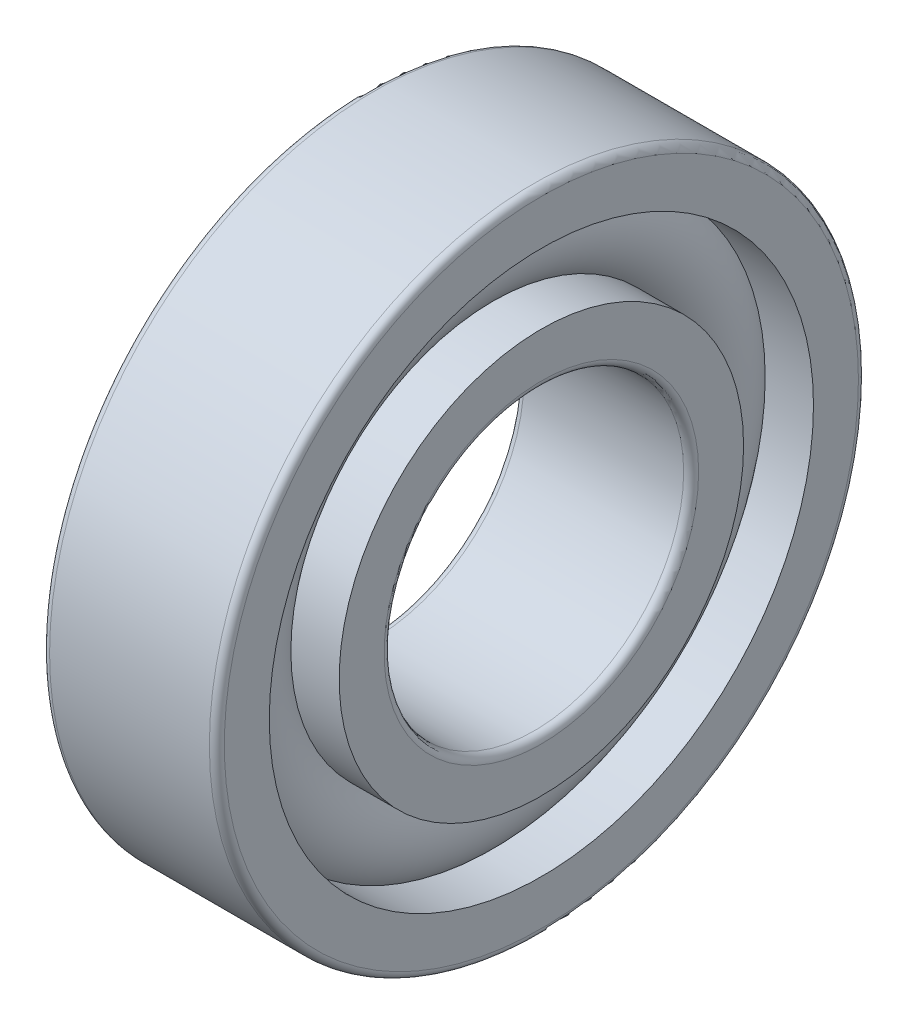
SolidWorks part; units mm, degrees
ref_plane "Plane1" through (0, 0, 0) normal (0, 0, 1) x (1, 0, 0)
ref_plane "Plane2" through (0, 0, 0) normal (0, 1, 0) x (1, 0, 0)
ref_plane "Plane3" through (0, 0, 0) normal (1, 0, 0) x (0, 0, -1)
other "Configuration Table"
sketch "Clipboard" plane through (0, 0, 0) normal (0, 0, 1) x (1, 0, 0)
  line L0 (-10, 0) -> (10, 0) construction
  line L1 (0, 0) -> (22.3471, -0.7804)
  line L2 (0, 0) -> (4.7471, 0.1658)
  line L3 (0, 0) -> (22.3471, -0.7804)
  line L4 (0, 0) -> (-22.3573, -0.3902)
  dimension "Count" = 2
sketch "CagSpiSke" plane through (0, 0, 0) normal (0, 0, 1) x (1, 0, 0)
  line L0 (0.105, 4.575) -> (0.105, 4.925)
  line L1 (0.105, 4.925) -> (-0.105, 4.925)
  line L2 (-0.105, 4.925) -> (-0.105, 4.575)
  line L3 (-0.105, 4.575) -> (0.105, 4.575)
  line L4 (-20.6375, 0) -> (20.6375, 0) construction
  line L5 (0, 0) -> (0, 23.7692) construction
revolve "CageSpine" add sketch "CagSpiSke" angle 0.001 about L4 reverse direction yes
ref_axis "Axis1" through (-50, 0, 0) along (1, 0, 0)
sketch "CagBalSke" plane through (0, 0, 0) normal (0, 0, 1) x (1, 0, 0)
  line L0 (-1.155, 4.75) -> (1.155, 4.75)
  line L1 (-1.905, 4.75) -> (1.905, 4.75) construction
  line L2 (-10, 0) -> (10, 0) construction
  line L3 (0, 0) -> (0, 24) construction
  arc A0 (1.155, 4.75) -> (-1.155, 4.75) centre (0, 4.75) cw
revolve "CageBall" [suppressed] add sketch "CagBalSke" angle 360 about L1 reverse direction yes
pattern_circular "CageBalls" [suppressed] count 2 every 180 about axis through (-50, 0, 0) along (1, 0, 0)
sketch "CagTrmODSke" plane through (0, 0, 0) normal (0, 0, 1) x (1, 0, 0)
  line L0 (1.156, 4.925) -> (1.156, 5.906)
  line L1 (1.156, 5.906) -> (-1.156, 5.906)
  line L2 (-1.156, 5.906) -> (-1.156, 4.925)
  line L3 (-1.156, 4.925) -> (1.156, 4.925)
  line L4 (-20.6375, 0) -> (20.6375, 0) construction
  line L5 (0, 0) -> (0, 25) construction
revolve "CageTrimOD" [suppressed] cut sketch "CagTrmODSke" angle 360 about L4 reverse direction yes
sketch "CagTrmIDSke" plane through (0, 0, 0) normal (0, 0, 1) x (1, 0, 0)
  line L0 (1.156, 3.596) -> (1.156, 4.575)
  line L1 (1.156, 4.575) -> (-1.156, 4.575)
  line L2 (-1.156, 4.575) -> (-1.156, 3.596)
  line L3 (-1.156, 3.596) -> (1.156, 3.596)
  line L4 (-20.6375, 0) -> (20.6375, 0) construction
  line L5 (0, 0) -> (0, 25) construction
revolve "CageTrimID" [suppressed] cut sketch "CagTrmIDSke" angle 360 about L4 reverse direction yes
sketch "BalSimSke" plane through (0, 0, 0) normal (0, 0, 1) x (1, 0, 0)
  line L0 (-10, 0) -> (10, 0) construction
  line L1 (-10, 4.75) -> (10, 4.75) construction
  line L2 (0, 0) -> (0, 23) construction
  circle A0 centre (0, 4.75) radius 1.05
revolve "BallsSimplified" add sketch "BalSimSke" angle 360 about L0
sketch "BalDetSke" plane through (0, 0, 0) normal (0, 0, 1) x (1, 0, 0)
  line L0 (-1.05, 4.75) -> (1.05, 4.75)
  line L1 (-1.905, 4.75) -> (1.905, 4.75) construction
  line L2 (0, 0) -> (0, 25) construction
  arc A0 (1.05, 4.75) -> (-1.05, 4.75) centre (0, 4.75) cw
revolve "BallDetailed" [suppressed] add sketch "BalDetSke" angle 360 about L1 reverse direction yes
sketch "InnRacSke" plane through (0, 0, 0) normal (0, 0, 1) x (1, 0, 0)
  line L0 (-0.7487, 4.05) -> (-1.75, 4.05)
  line L1 (-1.75, 4.05) -> (-1.75, 3.15)
  line L2 (-1.6, 3) -> (1.6, 3)
  line L3 (1.75, 3.15) -> (1.75, 4.05)
  line L4 (1.75, 4.05) -> (0.7487, 4.05)
  line L5 (-20.6375, 0) -> (20.6375, 0) construction
  line L6 (0, 0) -> (0, 30) construction
  arc A0 (-1.75, 3.15) -> (-1.6, 3) centre (-1.6, 3.15) ccw
  arc A1 (1.6, 3) -> (1.75, 3.15) centre (1.6, 3.15) ccw
  arc A2 (0.7487, 4.05) -> (-0.7487, 4.05) centre (0, 4.75) cw
revolve "InnerRace" add sketch "InnRacSke" angle 360 about L5 reverse direction yes
sketch "OutRacSke" plane through (0, 0, 0) normal (0, 0, 1) x (1, 0, 0)
  line L0 (-0.7487, 5.45) -> (-1.75, 5.45)
  line L1 (-1.75, 5.45) -> (-1.75, 6.35)
  line L2 (-1.6, 6.5) -> (1.6, 6.5)
  line L3 (1.75, 6.35) -> (1.75, 5.45)
  line L4 (1.75, 5.45) -> (0.7487, 5.45)
  line L5 (-20.6375, 0) -> (20.6375, 0) construction
  line L6 (0, 0) -> (0, 30) construction
  arc A0 (-1.75, 6.35) -> (-1.6, 6.5) centre (-1.6, 6.35) cw
  arc A1 (1.6, 6.5) -> (1.75, 6.35) centre (1.6, 6.35) cw
  arc A2 (0.7487, 5.45) -> (-0.7487, 5.45) centre (0, 4.75) ccw
revolve "OuterRace" add sketch "OutRacSke" angle 360 about L5 reverse direction yes
pattern_circular "BallsDetailed" [suppressed] count 2 every 180 about axis through (-50, 0, 0) along (1, 0, 0)
equation "\"BallCLRad@Clipboard\" = ( \"OD@OutRacSke\" + \"ID@InnRacSke\" ) / 4"
equation "\"BallCLRad@BalSimSke\" = \"BallCLRad@Clipboard\""
equation "\"BallCLRad@BalDetSke\" = \"BallCLRad@Clipboard\""
equation "\"BallCLRad@InnRacSke\" = \"BallCLRad@Clipboard\""
equation "\"BallCLRad@OutRacSke\" = \"BallCLRad@Clipboard\""
equation "\"Ball_diameter@InnRacSke\" = \"Ball_diameter@BalDetSke\" - 0.05"
equation "\"Ball_diameter@OutRacSke\" = \"Ball_diameter@BalDetSke\" - 0.05"
equation "\"Ball_diameter@BalSimSke\" = \"Ball_diameter@BalDetSke\""
equation "\"Width@OutRacSke\" = \"Width@InnRacSke\""
equation "\"Fillet_radius@OutRacSke\" = \"Fillet_radius@InnRacSke\""
equation "\"Max_count@Clipboard\" = int( 3.14159265 / atn(( \"Ball_diameter@BalDetSke\" / 2) / sqr( \"BallCLRad@Clipboard\"  *  \"BallCLRad@Clipboard\" - ( \"Ball_diameter@BalDetSke\" / 2) *  ( \"Ball_diameter@BalDetSke\" / 2))))"
equation "\"Max_count@Clipboard\" = ((sgn( \"Max_count@Clipboard\" - \"Count@Clipboard\" )-1)*( \"Max_count@Clipboard\" - \"Count@Clipboard\" ))/-2+ \"Count@Clipboard\""
equation "\"Count@BallsDetailed\" = int( \"Show_count@Clipboard\" ) "
equation "\"Count@BallsDetailed\" = ((sgn( \"Count@BallsDetailed\" - \"Max_count@Clipboard\" )-1)*( \"Count@BallsDetailed\" - \"Max_count@Clipboard\" ))/-2+ \"Max_count@Clipboard\""
equation "\"Count@BallsDetailed\" = ((sgn( \"Count@BallsDetailed\" - \"Min_count@Clipboard\" )+1)*( \"Count@BallsDetailed\" - \"Min_count@Clipboard\"))/2 +\"Min_count@Clipboard\""
equation "\"Angle@BallsDetailed\" = 360.0 / \"Max_count@Clipboard\""
equation "\"BallCLRad@CagBalSke\" = \"BallCLRad@Clipboard\""
equation "\"Count@CageBalls\" = \"Count@BallsDetailed\""
equation "\"Angle@CageBalls\" = \"Angle@BallsDetailed\""
equation "\"Angle@CageSpine\" =  \"Angle@CageBalls\" * ( \"Count@CageBalls\" -1 + int( \"Count@CageBalls\" / \"Max_count@Clipboard\" ) )  + 0.001 -  int( \"Count@CageBalls\" / \"Max_count@Clipboard\" ) * 0.001"
equation "\"Angle@CageSpine\" =  \"Angle@CageSpine\" * int( \"Min_count@Clipboard\" / 2) + int(1 / \"Min_count@Clipboard\")  * 0.001"
equation "\"CageWallOD@CagBalSke\" =  \"Ball_diameter@BalDetSke\" * 1.1"
equation "\"Thickness@CagSpiSke\" =  \"Ball_diameter@BalDetSke\" * 0.1"
equation "\"OD@CagTrmODSke\" = \"BallCLRad@Clipboard\" * 2 + \"CageWallOD@CagBalSke\" + 0.002"
equation "\"ID@CagTrmODSke\" = \"BallCLRad@Clipboard\" * 2 + \"Ball_diameter@BalDetSke\" / 6"
equation "\"OD@CagTrmIDSke\" = \"BallCLRad@Clipboard\" * 2 - \"Ball_diameter@BalDetSke\" / 6"
equation "\"ID@CagTrmIDSke\" = \"BallCLRad@Clipboard\" * 2 - \"CageWallOD@CagBalSke\" + 0.002"
equation "\"OD@CagSpiSke\" = \"ID@CagTrmODSke\""
equation "\"ID@CagSpiSke\" = \"OD@CagTrmIDSke\""
equation "\"Width@CagTrmODSke\" = \"CageWallOD@CagBalSke\" + 0.002"
equation "\"Width@CagTrmIDSke\" = \"CageWallOD@CagBalSke\" + 0.002"
